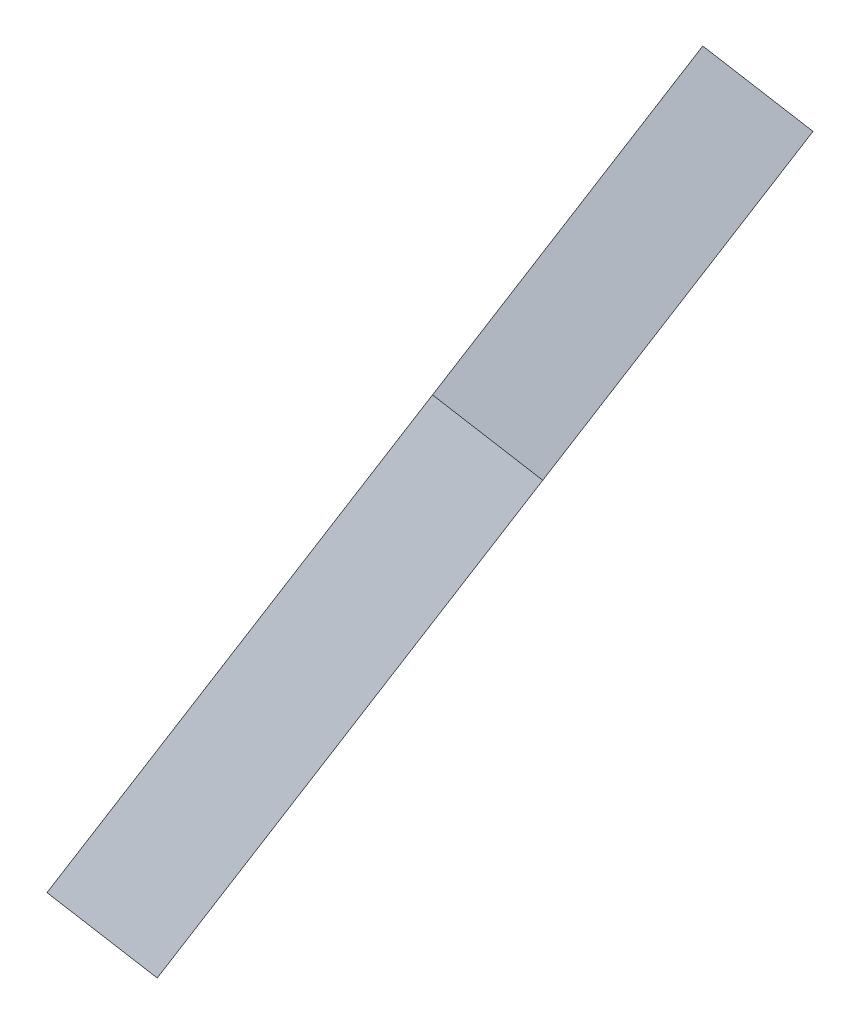
SolidWorks part; units mm, degrees
ref_plane "Front Plane" through (0, 0, 0) normal (0, 0, 1) x (1, 0, 0)
ref_plane "Top Plane" through (0, 0, 0) normal (0, 1, 0) x (1, 0, 0)
ref_plane "Right Plane" through (0, 0, 0) normal (1, 0, 0) x (0, 0, -1)
sketch "Sketch2" plane through (-19.8775, 12.285, 7.5925) normal (0.809, -0.5, -0.309) x (-0.2629, 0.1625, -0.9511)
  line L0 (-40.5434, 50.1677) -> (-37.5967, 49.6049)
  line L1 (-37.5967, 49.6049) -> (-38.3744, 45.5326)
  line L2 (-38.3744, 45.5326) -> (-41.669, 43.0158)
  line L3 (-41.669, 43.0158) -> (-43.4902, 45.3998)
  line L4 (-41.1062, 47.2209) -> (-57.2787, 34.8663) construction
  line L5 (-39.285, 44.837) -> (-55.4575, 32.4823) construction
  line L6 (-43.4902, 45.3998) -> (-51.4921, 39.2869)
  line L7 (-51.4921, 39.2869) -> (-60.4754, 50.6689)
  line L8 (-60.4754, 50.6689) -> (-52.8523, 63.0033)
  line L9 (-56.6638, 56.8361) -> (-38.3744, 45.5326) construction
  line L10 (-40.5434, 50.1677) -> (-43.4902, 45.3998) construction
  line L11 (-38.6545, 60.0586) -> (-52.8523, 63.0033)
  line L12 (-40.5434, 50.1677) -> (-38.6545, 60.0586)
  point P4 (-42.0168, 47.7837)
  dimension "D2" = 14.5
  dimension "D3" = 110
extrude "Boss-Extrude1" add sketch "Sketch2" along normal blind 3
equation "\"D1@Boss-Extrude1\"=\"T@d20.Assembly\""
